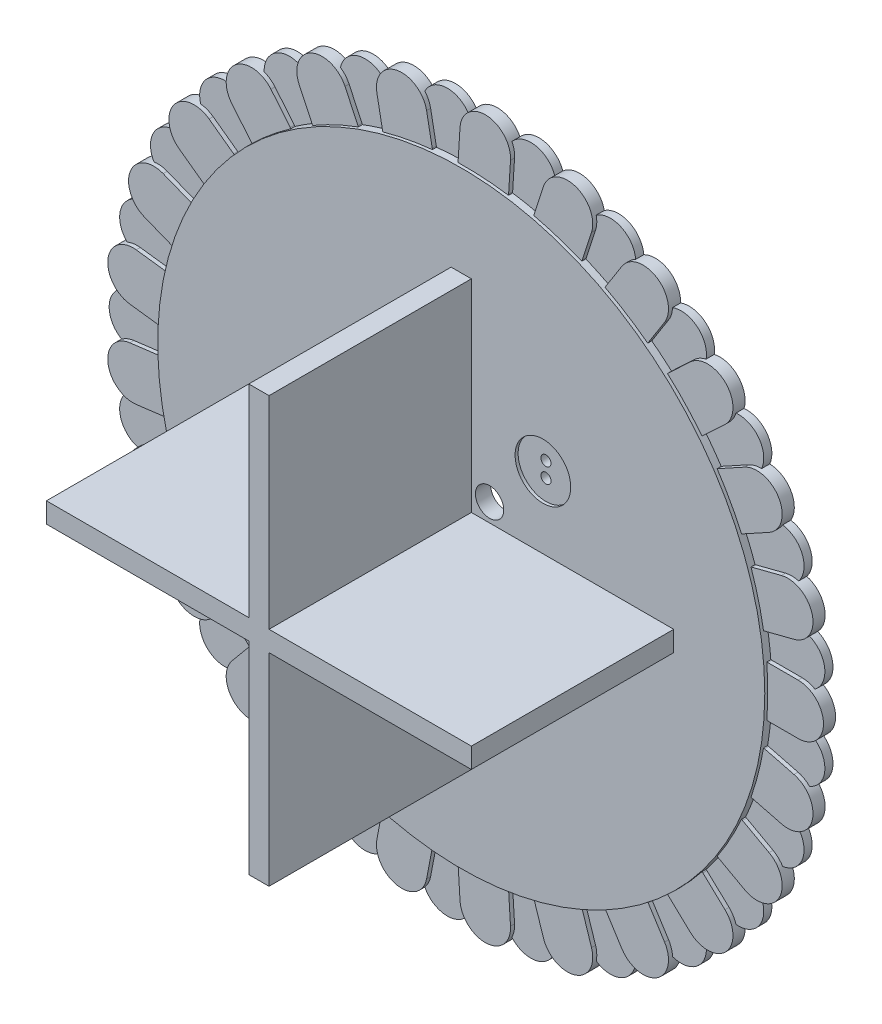
SolidWorks part; units mm, degrees
ref_plane "Front Plane" through (0, 0, 0) normal (0, 0, 1) x (1, 0, 0)
ref_plane "Top Plane" through (0, 0, 0) normal (0, 1, 0) x (1, 0, 0)
ref_plane "Right Plane" through (0, 0, 0) normal (1, 0, 0) x (0, 0, -1)
sketch "Schizzo1" plane through (0, 0, 0) normal (0, 0, 1) x (1, 0, 0)
  circle A0 centre (0, 0) radius 30
  dimension "D1" = 60
extrude "Estrusione-Estrusione1" add sketch "Schizzo1" along normal blind 1.5
sketch "Schizzo2" plane through (0, 0, 1.5) normal (0, 0, 1) x (1, 0, 0)
  line L0 (-1, 1) -> (-1, 21)
  line L1 (-21, 1) -> (-1, 1)
  line L2 (-21, 1) -> (-21, -1)
  line L3 (-21, -1) -> (-1, -1)
  line L4 (21, 1) -> (21, -1)
  line L5 (-1, 1) -> (1, -1) construction
  line L7 (1, -21) -> (-1, -21)
  line L8 (1, -21) -> (1, -1)
  line L9 (1, 21) -> (-1, 21)
  line L10 (-1, -21) -> (-1, -1)
  line L15 (1, 1) -> (1, 21)
  line L18 (1, 1) -> (21, 1)
  line L19 (1, -1) -> (21, -1)
  point P0 (0, 0)
  point P6 (0, 0)
  point P11 (0, 0)
  dimension "D1" = 20
  dimension "D2" = 2
extrude "Estrusione-Estrusione2" add sketch "Schizzo2" along normal blind 20
sketch "Schizzo3" plane through (0, 0, 1.5) normal (0, 0, 1) x (1, 0, 0)
  line L0 (-8.0711, 7.3211) -> (-8.0711, 8.8211) construction
  line L1 (-21, 0) -> (21, 0) construction
  line L2 (-0.2637, 0.2637) -> (-1.0137, 1.0137) construction
  line L4 (-21, 1) -> (-21, -1) construction
  line L5 (21, -1) -> (21, 1) construction
  line L6 (1, 21) -> (-1, 21) construction
  line L7 (0, 21) -> (0, -21) construction
  line L8 (-1, -21) -> (1, -21) construction
  circle A0 centre (-8.0711, 8.8211) radius 0.5
  circle A1 centre (-8.0711, 7.3211) radius 0.5
  circle A3 centre (-8.0711, 8.0711) radius 2.6 construction
  circle A4 centre (-8.0711, -8.8211) radius 0.5
  circle A5 centre (-8.0711, -7.3211) radius 0.5
  circle A6 centre (-8.0711, -8.0711) radius 2.6 construction
  circle A7 centre (8.0711, -8.8211) radius 0.5
  circle A8 centre (8.0711, -8.0711) radius 2.6 construction
  circle A9 centre (8.0711, -7.3211) radius 0.5
  circle A10 centre (8.0711, 8.8211) radius 0.5
  circle A11 centre (8.0711, 7.3211) radius 0.5
  circle A12 centre (8.0711, 8.0711) radius 2.6 construction
  dimension "D1" = 1.5
  dimension "D2" = 1
  dimension "D3" = 5.2
  dimension "D4" = 10
extrude "Taglio-Estrusione1" cut sketch "Schizzo3" against normal through all contours A1 | A0 | A11 | A10 | A5 | A4 | A7 | A9 region at (-8.0711, 8.8211, 1.5) region at (-8.0711, 7.3211, 1.5) region at (-8.0711, -8.8211, 1.5) region at (-8.0711, -7.3211, 1.5) region at (8.0711, -8.8211, 1.5) region at (8.0711, -7.3211, 1.5) region at (8.0711, 8.8211, 1.5) region at (8.0711, 7.3211, 1.5)
sketch "Schizzo4" plane through (0, 0, 1.5) normal (0, 0, 1) x (1, 0, 0)
  line L0 (-8.0711, -7.3211) -> (-8.0711, -8.8211) construction
  line L1 (-21, 0) -> (-4.4705, 0) construction
  line L2 (-21, 1) -> (-21, -1) construction
  line L3 (0, -21) -> (0, -5.0355) construction
  line L4 (-1, -21) -> (1, -21) construction
  circle A0 centre (-8.0711, -8.0711) radius 2.75
  circle A1 centre (8.0711, -8.0711) radius 2.75
  circle A2 centre (8.0711, 8.0711) radius 2.75
  circle A3 centre (-8.0711, 8.0711) radius 2.75
  dimension "D1" = 5.5
extrude "Taglio-Estrusione2" cut sketch "Schizzo4" against normal blind 0.3
sketch "Schizzo5" plane through (0, 0, 0) normal (0, 0, -1) x (-1, 0, 0)
  line L0 (-30, 0) -> (-33, 0) construction
  line L1 (-30, -2.5) -> (-33, -2.5)
  line L2 (-30, 2.5) -> (-33, 2.5)
  line L3 (-29.4501, 6.2403) -> (-32.4265, 6.6163)
  line L4 (-30.0768, 1.2797) -> (-33.0531, 1.6557)
  line L5 (-29.7634, 3.76) -> (-32.7398, 4.136) construction
  line L6 (-28.4358, 9.8822) -> (-31.3415, 10.6282)
  line L7 (-29.6792, 5.0392) -> (-32.585, 5.7853)
  line L8 (-29.0575, 7.4607) -> (-31.9632, 8.2068) construction
  line L9 (-26.973, 13.3682) -> (-29.7623, 14.4726)
  line L10 (-28.8136, 8.7193) -> (-31.6029, 9.8237)
  line L11 (-27.8933, 11.0437) -> (-30.6826, 12.1481) construction
  line L12 (-25.0848, 16.6434) -> (-27.7137, 18.0886)
  line L13 (-27.4936, 12.2618) -> (-30.1225, 13.7071)
  line L14 (-26.2892, 14.4526) -> (-28.9181, 15.8979) construction
  line L15 (-22.801, 19.6561) -> (-25.2281, 21.4195)
  line L16 (-25.74, 15.611) -> (-28.167, 17.3744)
  line L17 (-24.2705, 17.6336) -> (-26.6976, 19.3969) construction
  line L18 (-20.1577, 22.3588) -> (-22.3446, 24.4125)
  line L19 (-23.5804, 18.714) -> (-25.7673, 20.7676)
  line L20 (-21.8691, 20.5364) -> (-24.056, 22.5901) construction
  line L21 (-17.1964, 24.709) -> (-19.1087, 27.0205)
  line L22 (-21.049, 21.5218) -> (-22.9613, 23.8334)
  line L23 (-19.1227, 23.1154) -> (-21.035, 25.4269) construction
  line L24 (-13.964, 26.6694) -> (-15.5715, 29.2024)
  line L25 (-18.1856, 23.9903) -> (-19.7931, 26.5233)
  line L26 (-16.0748, 25.3298) -> (-17.6823, 27.8628) construction
  line L27 (-10.5113, 28.2093) -> (-11.7886, 30.9237)
  line L28 (-15.0354, 26.0804) -> (-16.3128, 28.7948)
  line L29 (-12.7734, 27.1448) -> (-14.0507, 29.8593) construction
  line L30 (-6.8929, 29.3042) -> (-7.8199, 32.1574)
  line L31 (-11.6482, 27.7592) -> (-12.5752, 30.6123)
  line L32 (-9.2705, 28.5317) -> (-10.1976, 31.3849) construction
  line L33 (-3.1657, 29.9371) -> (-3.7279, 32.8839)
  line L34 (-8.0772, 29.0002) -> (-8.6393, 31.947)
  line L35 (-5.6214, 29.4686) -> (-6.1836, 32.4155) construction
  line L36 (0.6114, 30.0978) -> (0.423, 33.0919)
  line L37 (-4.3788, 29.7838) -> (-4.5672, 32.7779)
  line L38 (-1.8837, 29.9408) -> (-2.0721, 32.9349) construction
  line L39 (4.3788, 29.7838) -> (4.5672, 32.7779)
  line L40 (-0.6114, 30.0978) -> (-0.423, 33.0919)
  line L41 (1.8837, 29.9408) -> (2.0721, 32.9349) construction
  line L42 (8.0772, 29.0002) -> (8.6393, 31.947)
  line L43 (3.1657, 29.9371) -> (3.7279, 32.8839)
  line L44 (5.6214, 29.4686) -> (6.1836, 32.4155) construction
  line L45 (11.6482, 27.7592) -> (12.5752, 30.6123)
  line L46 (6.8929, 29.3042) -> (7.8199, 32.1574)
  line L47 (9.2705, 28.5317) -> (10.1976, 31.3849) construction
  line L48 (15.0354, 26.0804) -> (16.3128, 28.7948)
  line L49 (10.5113, 28.2093) -> (11.7886, 30.9237)
  line L50 (12.7734, 27.1448) -> (14.0507, 29.8593) construction
  line L51 (18.1856, 23.9903) -> (19.7931, 26.5233)
  line L52 (13.964, 26.6694) -> (15.5715, 29.2024)
  line L53 (16.0748, 25.3298) -> (17.6823, 27.8628) construction
  line L54 (21.049, 21.5218) -> (22.9613, 23.8334)
  line L55 (17.1964, 24.709) -> (19.1087, 27.0205)
  line L56 (19.1227, 23.1154) -> (21.035, 25.4269) construction
  line L57 (23.5804, 18.714) -> (25.7673, 20.7676)
  line L58 (20.1577, 22.3588) -> (22.3446, 24.4125)
  line L59 (21.8691, 20.5364) -> (24.056, 22.5901) construction
  line L60 (25.74, 15.611) -> (28.167, 17.3744)
  line L61 (22.801, 19.6561) -> (25.2281, 21.4195)
  line L62 (24.2705, 17.6336) -> (26.6976, 19.3969) construction
  line L63 (27.4936, 12.2618) -> (30.1225, 13.7071)
  line L64 (25.0848, 16.6434) -> (27.7137, 18.0886)
  line L65 (26.2892, 14.4526) -> (28.9181, 15.8979) construction
  line L66 (28.8136, 8.7193) -> (31.6029, 9.8237)
  line L67 (26.973, 13.3682) -> (29.7623, 14.4726)
  line L68 (27.8933, 11.0437) -> (30.6826, 12.1481) construction
  line L69 (29.6792, 5.0392) -> (32.585, 5.7853)
  line L70 (28.4358, 9.8822) -> (31.3415, 10.6282)
  line L71 (29.0575, 7.4607) -> (31.9632, 8.2068) construction
  line L72 (30.0768, 1.2797) -> (33.0531, 1.6557)
  line L73 (29.4501, 6.2403) -> (32.4265, 6.6163)
  line L74 (29.7634, 3.76) -> (32.7398, 4.136) construction
  line L75 (30, -2.5) -> (33, -2.5)
  line L76 (30, 2.5) -> (33, 2.5)
  line L77 (30, 0) -> (33, 0) construction
  line L78 (29.4501, -6.2403) -> (32.4265, -6.6163)
  line L79 (30.0768, -1.2797) -> (33.0531, -1.6557)
  line L80 (29.7634, -3.76) -> (32.7398, -4.136) construction
  line L81 (28.4358, -9.8822) -> (31.3415, -10.6282)
  line L82 (29.6792, -5.0392) -> (32.585, -5.7853)
  line L83 (29.0575, -7.4607) -> (31.9632, -8.2068) construction
  line L84 (26.973, -13.3682) -> (29.7623, -14.4726)
  line L85 (28.8136, -8.7193) -> (31.6029, -9.8237)
  line L86 (27.8933, -11.0437) -> (30.6826, -12.1481) construction
  line L87 (25.0848, -16.6434) -> (27.7137, -18.0886)
  line L88 (27.4936, -12.2618) -> (30.1225, -13.7071)
  line L89 (26.2892, -14.4526) -> (28.9181, -15.8979) construction
  line L90 (22.801, -19.6561) -> (25.2281, -21.4195)
  line L91 (25.74, -15.611) -> (28.167, -17.3744)
  line L92 (24.2705, -17.6336) -> (26.6976, -19.3969) construction
  line L93 (20.1577, -22.3588) -> (22.3446, -24.4125)
  line L94 (23.5804, -18.714) -> (25.7673, -20.7676)
  line L95 (21.8691, -20.5364) -> (24.056, -22.5901) construction
  line L96 (17.1964, -24.709) -> (19.1087, -27.0205)
  line L97 (21.049, -21.5218) -> (22.9613, -23.8334)
  line L98 (19.1227, -23.1154) -> (21.035, -25.4269) construction
  line L99 (13.964, -26.6694) -> (15.5715, -29.2024)
  line L100 (18.1856, -23.9903) -> (19.7931, -26.5233)
  line L101 (16.0748, -25.3298) -> (17.6823, -27.8628) construction
  line L102 (10.5113, -28.2093) -> (11.7886, -30.9237)
  line L103 (15.0354, -26.0804) -> (16.3128, -28.7948)
  line L104 (12.7734, -27.1448) -> (14.0507, -29.8593) construction
  line L105 (6.8929, -29.3042) -> (7.8199, -32.1574)
  line L106 (11.6482, -27.7592) -> (12.5752, -30.6123)
  line L107 (9.2705, -28.5317) -> (10.1976, -31.3849) construction
  line L108 (3.1657, -29.9371) -> (3.7279, -32.8839)
  line L109 (8.0772, -29.0002) -> (8.6393, -31.947)
  line L110 (5.6214, -29.4686) -> (6.1836, -32.4155) construction
  line L111 (-0.6114, -30.0978) -> (-0.423, -33.0919)
  line L112 (4.3788, -29.7838) -> (4.5672, -32.7779)
  line L113 (1.8837, -29.9408) -> (2.0721, -32.9349) construction
  line L114 (-4.3788, -29.7838) -> (-4.5672, -32.7779)
  line L115 (0.6114, -30.0978) -> (0.423, -33.0919)
  line L116 (-1.8837, -29.9408) -> (-2.0721, -32.9349) construction
  line L117 (-8.0772, -29.0002) -> (-8.6393, -31.947)
  line L118 (-3.1657, -29.9371) -> (-3.7279, -32.8839)
  line L119 (-5.6214, -29.4686) -> (-6.1836, -32.4155) construction
  line L120 (-11.6482, -27.7592) -> (-12.5752, -30.6123)
  line L121 (-6.8929, -29.3042) -> (-7.8199, -32.1574)
  line L122 (-9.2705, -28.5317) -> (-10.1976, -31.3849) construction
  line L123 (-15.0354, -26.0804) -> (-16.3128, -28.7948)
  line L124 (-10.5113, -28.2093) -> (-11.7886, -30.9237)
  line L125 (-12.7734, -27.1448) -> (-14.0507, -29.8593) construction
  line L126 (-18.1856, -23.9903) -> (-19.7931, -26.5233)
  line L127 (-13.964, -26.6694) -> (-15.5715, -29.2024)
  line L128 (-16.0748, -25.3298) -> (-17.6823, -27.8628) construction
  line L129 (-21.049, -21.5218) -> (-22.9613, -23.8334)
  line L130 (-17.1964, -24.709) -> (-19.1087, -27.0205)
  line L131 (-19.1227, -23.1154) -> (-21.035, -25.4269) construction
  line L132 (-23.5804, -18.714) -> (-25.7673, -20.7676)
  line L133 (-20.1577, -22.3588) -> (-22.3446, -24.4125)
  line L134 (-21.8691, -20.5364) -> (-24.056, -22.5901) construction
  line L135 (-25.74, -15.611) -> (-28.167, -17.3744)
  line L136 (-22.801, -19.6561) -> (-25.2281, -21.4195)
  line L137 (-24.2705, -17.6336) -> (-26.6976, -19.3969) construction
  line L138 (-27.4936, -12.2618) -> (-30.1225, -13.7071)
  line L139 (-25.0848, -16.6434) -> (-27.7137, -18.0886)
  line L140 (-26.2892, -14.4526) -> (-28.9181, -15.8979) construction
  line L141 (-28.8136, -8.7193) -> (-31.6029, -9.8237)
  line L142 (-26.973, -13.3682) -> (-29.7623, -14.4726)
  line L143 (-27.8933, -11.0437) -> (-30.6826, -12.1481) construction
  line L144 (-29.6792, -5.0392) -> (-32.585, -5.7853)
  line L145 (-28.4358, -9.8822) -> (-31.3415, -10.6282)
  line L146 (-29.0575, -7.4607) -> (-31.9632, -8.2068) construction
  line L147 (-30.0768, -1.2797) -> (-33.0531, -1.6557)
  line L148 (-29.4501, -6.2403) -> (-32.4265, -6.6163)
  line L149 (-29.7634, -3.76) -> (-32.7398, -4.136) construction
  circle A0 centre (0, 0) radius 30 construction
  arc A1 (-30, -2.5) -> (-30, 2.5) centre (-30, 0) ccw
  arc A2 (-33, 2.5) -> (-33, -2.5) centre (-33, 0) ccw
  arc A3 (-30.0768, 1.2797) -> (-29.4501, 6.2403) centre (-29.7634, 3.76) ccw
  arc A4 (-32.4265, 6.6163) -> (-33.0531, 1.6557) centre (-32.7398, 4.136) ccw
  arc A5 (-29.6792, 5.0392) -> (-28.4358, 9.8822) centre (-29.0575, 7.4607) ccw
  arc A6 (-31.3415, 10.6282) -> (-32.585, 5.7853) centre (-31.9632, 8.2068) ccw
  arc A7 (-28.8136, 8.7193) -> (-26.973, 13.3682) centre (-27.8933, 11.0437) ccw
  arc A8 (-29.7623, 14.4726) -> (-31.6029, 9.8237) centre (-30.6826, 12.1481) ccw
  arc A9 (-27.4936, 12.2618) -> (-25.0848, 16.6434) centre (-26.2892, 14.4526) ccw
  arc A10 (-27.7137, 18.0886) -> (-30.1225, 13.7071) centre (-28.9181, 15.8979) ccw
  arc A11 (-25.74, 15.611) -> (-22.801, 19.6561) centre (-24.2705, 17.6336) ccw
  arc A12 (-25.2281, 21.4195) -> (-28.167, 17.3744) centre (-26.6976, 19.3969) ccw
  arc A13 (-23.5804, 18.714) -> (-20.1577, 22.3588) centre (-21.8691, 20.5364) ccw
  arc A14 (-22.3446, 24.4125) -> (-25.7673, 20.7676) centre (-24.056, 22.5901) ccw
  arc A15 (-21.049, 21.5218) -> (-17.1964, 24.709) centre (-19.1227, 23.1154) ccw
  arc A16 (-19.1087, 27.0205) -> (-22.9613, 23.8334) centre (-21.035, 25.4269) ccw
  arc A17 (-18.1856, 23.9903) -> (-13.964, 26.6694) centre (-16.0748, 25.3298) ccw
  arc A18 (-15.5715, 29.2024) -> (-19.7931, 26.5233) centre (-17.6823, 27.8628) ccw
  arc A19 (-15.0354, 26.0804) -> (-10.5113, 28.2093) centre (-12.7734, 27.1448) ccw
  arc A20 (-11.7886, 30.9237) -> (-16.3128, 28.7948) centre (-14.0507, 29.8593) ccw
  arc A21 (-11.6482, 27.7592) -> (-6.8929, 29.3042) centre (-9.2705, 28.5317) ccw
  arc A22 (-7.8199, 32.1574) -> (-12.5752, 30.6123) centre (-10.1976, 31.3849) ccw
  arc A23 (-8.0772, 29.0002) -> (-3.1657, 29.9371) centre (-5.6214, 29.4686) ccw
  arc A24 (-3.7279, 32.8839) -> (-8.6393, 31.947) centre (-6.1836, 32.4155) ccw
  arc A25 (-4.3788, 29.7838) -> (0.6114, 30.0978) centre (-1.8837, 29.9408) ccw
  arc A26 (0.423, 33.0919) -> (-4.5672, 32.7779) centre (-2.0721, 32.9349) ccw
  arc A27 (-0.6114, 30.0978) -> (4.3788, 29.7838) centre (1.8837, 29.9408) ccw
  arc A28 (4.5672, 32.7779) -> (-0.423, 33.0919) centre (2.0721, 32.9349) ccw
  arc A29 (3.1657, 29.9371) -> (8.0772, 29.0002) centre (5.6214, 29.4686) ccw
  arc A30 (8.6393, 31.947) -> (3.7279, 32.8839) centre (6.1836, 32.4155) ccw
  arc A31 (6.8929, 29.3042) -> (11.6482, 27.7592) centre (9.2705, 28.5317) ccw
  arc A32 (12.5752, 30.6123) -> (7.8199, 32.1574) centre (10.1976, 31.3849) ccw
  arc A33 (10.5113, 28.2093) -> (15.0354, 26.0804) centre (12.7734, 27.1448) ccw
  arc A34 (16.3128, 28.7948) -> (11.7886, 30.9237) centre (14.0507, 29.8593) ccw
  arc A35 (13.964, 26.6694) -> (18.1856, 23.9903) centre (16.0748, 25.3298) ccw
  arc A36 (19.7931, 26.5233) -> (15.5715, 29.2024) centre (17.6823, 27.8628) ccw
  arc A37 (17.1964, 24.709) -> (21.049, 21.5218) centre (19.1227, 23.1154) ccw
  arc A38 (22.9613, 23.8334) -> (19.1087, 27.0205) centre (21.035, 25.4269) ccw
  arc A39 (20.1577, 22.3588) -> (23.5804, 18.714) centre (21.8691, 20.5364) ccw
  arc A40 (25.7673, 20.7676) -> (22.3446, 24.4125) centre (24.056, 22.5901) ccw
  arc A41 (22.801, 19.6561) -> (25.74, 15.611) centre (24.2705, 17.6336) ccw
  arc A42 (28.167, 17.3744) -> (25.2281, 21.4195) centre (26.6976, 19.3969) ccw
  arc A43 (25.0848, 16.6434) -> (27.4936, 12.2618) centre (26.2892, 14.4526) ccw
  arc A44 (30.1225, 13.7071) -> (27.7137, 18.0886) centre (28.9181, 15.8979) ccw
  arc A45 (26.973, 13.3682) -> (28.8136, 8.7193) centre (27.8933, 11.0437) ccw
  arc A46 (31.6029, 9.8237) -> (29.7623, 14.4726) centre (30.6826, 12.1481) ccw
  arc A47 (28.4358, 9.8822) -> (29.6792, 5.0392) centre (29.0575, 7.4607) ccw
  arc A48 (32.585, 5.7853) -> (31.3415, 10.6282) centre (31.9632, 8.2068) ccw
  arc A49 (29.4501, 6.2403) -> (30.0768, 1.2797) centre (29.7634, 3.76) ccw
  arc A50 (33.0531, 1.6557) -> (32.4265, 6.6163) centre (32.7398, 4.136) ccw
  arc A51 (30, 2.5) -> (30, -2.5) centre (30, 0) ccw
  arc A52 (33, -2.5) -> (33, 2.5) centre (33, 0) ccw
  arc A53 (30.0768, -1.2797) -> (29.4501, -6.2403) centre (29.7634, -3.76) ccw
  arc A54 (32.4265, -6.6163) -> (33.0531, -1.6557) centre (32.7398, -4.136) ccw
  arc A55 (29.6792, -5.0392) -> (28.4358, -9.8822) centre (29.0575, -7.4607) ccw
  arc A56 (31.3415, -10.6282) -> (32.585, -5.7853) centre (31.9632, -8.2068) ccw
  arc A57 (28.8136, -8.7193) -> (26.973, -13.3682) centre (27.8933, -11.0437) ccw
  arc A58 (29.7623, -14.4726) -> (31.6029, -9.8237) centre (30.6826, -12.1481) ccw
  arc A59 (27.4936, -12.2618) -> (25.0848, -16.6434) centre (26.2892, -14.4526) ccw
  arc A60 (27.7137, -18.0886) -> (30.1225, -13.7071) centre (28.9181, -15.8979) ccw
  arc A61 (25.74, -15.611) -> (22.801, -19.6561) centre (24.2705, -17.6336) ccw
  arc A62 (25.2281, -21.4195) -> (28.167, -17.3744) centre (26.6976, -19.3969) ccw
  arc A63 (23.5804, -18.714) -> (20.1577, -22.3588) centre (21.8691, -20.5364) ccw
  arc A64 (22.3446, -24.4125) -> (25.7673, -20.7676) centre (24.056, -22.5901) ccw
  arc A65 (21.049, -21.5218) -> (17.1964, -24.709) centre (19.1227, -23.1154) ccw
  arc A66 (19.1087, -27.0205) -> (22.9613, -23.8334) centre (21.035, -25.4269) ccw
  arc A67 (18.1856, -23.9903) -> (13.964, -26.6694) centre (16.0748, -25.3298) ccw
  arc A68 (15.5715, -29.2024) -> (19.7931, -26.5233) centre (17.6823, -27.8628) ccw
  arc A69 (15.0354, -26.0804) -> (10.5113, -28.2093) centre (12.7734, -27.1448) ccw
  arc A70 (11.7886, -30.9237) -> (16.3128, -28.7948) centre (14.0507, -29.8593) ccw
  arc A71 (11.6482, -27.7592) -> (6.8929, -29.3042) centre (9.2705, -28.5317) ccw
  arc A72 (7.8199, -32.1574) -> (12.5752, -30.6123) centre (10.1976, -31.3849) ccw
  arc A73 (8.0772, -29.0002) -> (3.1657, -29.9371) centre (5.6214, -29.4686) ccw
  arc A74 (3.7279, -32.8839) -> (8.6393, -31.947) centre (6.1836, -32.4155) ccw
  arc A75 (4.3788, -29.7838) -> (-0.6114, -30.0978) centre (1.8837, -29.9408) ccw
  arc A76 (-0.423, -33.0919) -> (4.5672, -32.7779) centre (2.0721, -32.9349) ccw
  arc A77 (0.6114, -30.0978) -> (-4.3788, -29.7838) centre (-1.8837, -29.9408) ccw
  arc A78 (-4.5672, -32.7779) -> (0.423, -33.0919) centre (-2.0721, -32.9349) ccw
  arc A79 (-3.1657, -29.9371) -> (-8.0772, -29.0002) centre (-5.6214, -29.4686) ccw
  arc A80 (-8.6393, -31.947) -> (-3.7279, -32.8839) centre (-6.1836, -32.4155) ccw
  arc A81 (-6.8929, -29.3042) -> (-11.6482, -27.7592) centre (-9.2705, -28.5317) ccw
  arc A82 (-12.5752, -30.6123) -> (-7.8199, -32.1574) centre (-10.1976, -31.3849) ccw
  arc A83 (-10.5113, -28.2093) -> (-15.0354, -26.0804) centre (-12.7734, -27.1448) ccw
  arc A84 (-16.3128, -28.7948) -> (-11.7886, -30.9237) centre (-14.0507, -29.8593) ccw
  arc A85 (-13.964, -26.6694) -> (-18.1856, -23.9903) centre (-16.0748, -25.3298) ccw
  arc A86 (-19.7931, -26.5233) -> (-15.5715, -29.2024) centre (-17.6823, -27.8628) ccw
  arc A87 (-17.1964, -24.709) -> (-21.049, -21.5218) centre (-19.1227, -23.1154) ccw
  arc A88 (-22.9613, -23.8334) -> (-19.1087, -27.0205) centre (-21.035, -25.4269) ccw
  arc A89 (-20.1577, -22.3588) -> (-23.5804, -18.714) centre (-21.8691, -20.5364) ccw
  arc A90 (-25.7673, -20.7676) -> (-22.3446, -24.4125) centre (-24.056, -22.5901) ccw
  arc A91 (-22.801, -19.6561) -> (-25.74, -15.611) centre (-24.2705, -17.6336) ccw
  arc A92 (-28.167, -17.3744) -> (-25.2281, -21.4195) centre (-26.6976, -19.3969) ccw
  arc A93 (-25.0848, -16.6434) -> (-27.4936, -12.2618) centre (-26.2892, -14.4526) ccw
  arc A94 (-30.1225, -13.7071) -> (-27.7137, -18.0886) centre (-28.9181, -15.8979) ccw
  arc A95 (-26.973, -13.3682) -> (-28.8136, -8.7193) centre (-27.8933, -11.0437) ccw
  arc A96 (-31.6029, -9.8237) -> (-29.7623, -14.4726) centre (-30.6826, -12.1481) ccw
  arc A97 (-28.4358, -9.8822) -> (-29.6792, -5.0392) centre (-29.0575, -7.4607) ccw
  arc A98 (-32.585, -5.7853) -> (-31.3415, -10.6282) centre (-31.9632, -8.2068) ccw
  arc A99 (-29.4501, -6.2403) -> (-30.0768, -1.2797) centre (-29.7634, -3.76) ccw
  arc A100 (-33.0531, -1.6557) -> (-32.4265, -6.6163) centre (-32.7398, -4.136) ccw
  point P6 (-31.5, 0)
  point P16 (-31.2516, 3.948)
  point P23 (-30.5104, 7.8337)
  point P30 (-29.288, 11.5959)
  point P37 (-27.6037, 15.1752)
  point P44 (-25.484, 18.5152)
  point P51 (-22.9625, 21.5632)
  point P58 (-20.0789, 24.2712)
  point P65 (-16.8785, 26.5963)
  point P72 (-13.412, 28.5021)
  point P79 (-9.734, 29.9583)
  point P86 (-5.9025, 30.942)
  point P93 (-1.9779, 31.4378)
  point P100 (1.9779, 31.4378)
  point P107 (5.9025, 30.942)
  point P114 (9.734, 29.9583)
  point P121 (13.412, 28.5021)
  point P128 (16.8785, 26.5963)
  point P135 (20.0789, 24.2712)
  point P142 (22.9625, 21.5632)
  point P149 (25.484, 18.5152)
  point P156 (27.6037, 15.1752)
  point P163 (29.288, 11.5959)
  point P170 (30.5104, 7.8337)
  point P177 (31.2516, 3.948)
  point P184 (31.5, 0)
  point P191 (31.2516, -3.948)
  point P198 (30.5104, -7.8337)
  point P205 (29.288, -11.5959)
  point P212 (27.6037, -15.1752)
  point P219 (25.484, -18.5152)
  point P226 (22.9625, -21.5632)
  point P233 (20.0789, -24.2712)
  point P240 (16.8785, -26.5963)
  point P247 (13.412, -28.5021)
  point P254 (9.734, -29.9583)
  point P261 (5.9025, -30.942)
  point P268 (1.9779, -31.4378)
  point P275 (-1.9779, -31.4378)
  point P282 (-5.9025, -30.942)
  point P289 (-9.734, -29.9583)
  point P296 (-13.412, -28.5021)
  point P303 (-16.8785, -26.5963)
  point P310 (-20.0789, -24.2712)
  point P317 (-22.9625, -21.5632)
  point P324 (-25.484, -18.5152)
  point P331 (-27.6037, -15.1752)
  point P338 (-29.288, -11.5959)
  point P345 (-30.5104, -7.8337)
  point P352 (-31.2516, -3.948)
  point P357 (0, 0)
  circle M206 centre (0, 0) radius 30
  dimension "D1" = 5
  dimension "D2" = 3
  dimension "D4" = 4.136
  dimension "D5" = 0.2602
  dimension "D3" = 50
extrude "Estrusione-Estrusione3" add sketch "Schizzo5" against normal blind 0.8 contours A6 A4 A2 L2 A1 A5 L7 M206 | A10 A8 A6 L6 A5 A9 L13 M206 | A14 A12 A10 L12 A9 A13 L19 M206 | A18 A16 A14 L18 A13 A17 L25 M206 | A22 A20 A18 L24 A17 A21 L31 M206 | A26 A24 A22 L30 A21 A25 L37 M206 | A30 A28 A26 L36 A25 A29 L43 M206 | A34 A32 A30 L42 A29 A33 L49 M206 | A38 A36 A34 L48 A33 A37 L55 M206 | A42 A40 A38 L54 A37 A41 L61 M206 | A46 A44 A42 L60 A41 A45 L67 M206 | A50 A48 A46 L66 A45 A49 L73 M206 | A54 A52 A50 L72 A49 A53 L79 M206 | A58 A56 A54 L78 A53 A57 L85 M206 | A62 A60 A58 L84 A57 A61 L91 M206 | A66 A64 A62 L90 A61 A65 L97 M206 | A70 A68 A66 L96 A65 A69 L103 M206 | A74 A72 A70 L102 A69 A73 L109 M206 | A78 A76 A74 L108 A73 A77 L115 M206 | A82 A80 A78 L114 A77 A81 L121 M206 | A86 A84 A82 L120 A81 A85 L127 M206 | A90 A88 A86 L126 A85 A89 L133 M206 | A94 A92 A90 L132 A89 A93 L139 M206 | A98 A96 A94 L138 A93 A97 L145 M206 | A2 A100 A98 L144 A97 A1 L1 M206 region at (32.5734, -4.115, 0) region at (32.5734, 4.115, 0) region at (30.5267, -12.0864, 0) region at (30.5267, 12.0864, 0) region at (26.5619, -19.2983, 0) region at (26.5619, 19.2983, 0) region at (20.9281, -25.2977, 0) region at (20.9281, 25.2977, 0) region at (13.9793, -29.7075, 0) region at (13.9793, 29.7075, 0) region at (6.1522, -32.2507, 0) region at (6.1522, 32.2507, 0) region at (-2.0616, -32.7675, 0) region at (-2.0616, 32.7675, 0) region at (-10.1457, -31.2254, 0) region at (-10.1457, 31.2254, 0) region at (-17.5924, -27.7212, 0) region at (-17.5924, 27.7212, 0) region at (-23.9337, -22.4752, 0) region at (-23.9337, 22.4752, 0) region at (-28.7711, -15.8171, 0) region at (-28.7711, 15.8171, 0) region at (-31.8008, -8.1651, 0) region at (-31.8008, 8.1651, 0) region at (-32.8323, 0, 0)
extrude "Estrusione-Estrusione4" add sketch "Schizzo5<3>" against normal blind 1.2 contours A9 L12 A10 L13 | A13 L18 A14 L19 | A17 L24 A18 L25 | A21 L30 A22 L31 | A25 L36 A26 L37 | A29 L42 A30 L43 | A33 L48 A34 L49 | A37 L54 A38 L55 | A41 L60 A42 L61 | A45 L66 A46 L67 | A49 L72 A50 L73 | A53 L78 A54 L79 | A57 L84 A58 L85 | A61 L90 A62 L91 | A65 L96 A66 L97 | A69 L102 A70 L103 | A73 L108 A74 L109 | A77 L114 A78 L115 | A81 L120 A82 L121 | A85 L126 A86 L127 | A89 L132 A90 L133 | A93 L138 A94 L139 | A97 L144 A98 L145 | A1 L2 A2 L1 | A5 L6 A6 L7
sketch "Schizzo5<3>" plane through (0, 0, 0) normal (0, 0, -1) x (-1, 0, 0) same geometry as "Schizzo5"
sketch "Schizzo6" plane through (0, 0, 1.5) normal (0, 0, 1) x (1, 0, 0)
  line L0 (-22.5607, 0) -> (21.4273, 0) construction
  line L1 (0, 12.6583) -> (0, -8.7601) construction
  circle A0 centre (-2.8, 2.8) radius 1.4
  circle A1 centre (-2.8, -2.8) radius 1.4
  circle A2 centre (2.8, -2.8) radius 1.4
  circle A3 centre (2.8, 2.8) radius 1.4
  dimension "D3" = 2.8
  dimension "D1" = 2.8
  dimension "D2" = 2.8
extrude "Taglio-Estrusione3" cut sketch "Schizzo6" against normal through all
